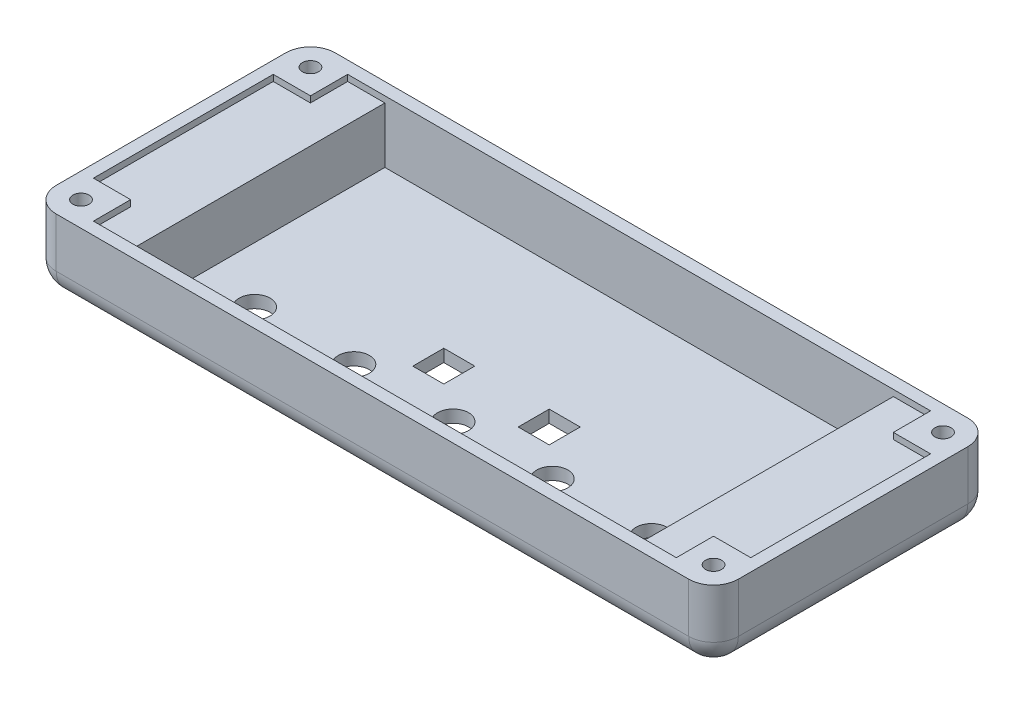
SolidWorks part; units mm, degrees
ref_plane "Front Plane" through (0, 0, 0) normal (0, 0, 1) x (1, 0, 0)
ref_plane "Top Plane" through (0, 0, 0) normal (0, 1, 0) x (1, 0, 0)
ref_plane "Right Plane" through (0, 0, 0) normal (1, 0, 0) x (0, 0, -1)
sketch "Sketch1" plane through (0, 0, 0) normal (0, 1, 0) x (1, 0, 0)
  line L1 (-55, 22.5) -> (55, 22.5)
  line L2 (-55, 22.5) -> (-55, -22.5)
  line L3 (-55, -22.5) -> (55, -22.5)
  line L4 (55, 22.5) -> (55, -22.5)
  line L5 (-55, 22.5) -> (55, -22.5) construction
  line L6 (-55, -22.5) -> (55, 22.5) construction
  point P0 (0, 0)
  dimension "D1" = 45
  dimension "D2" = 110
extrude "Boss-Extrude1" add sketch "Sketch1" along normal blind 2
sketch "Sketch3" plane through (0, 2, 0) normal (0, 1, 0) x (1, 0, 0)
  line L1 (-55, 22.5) -> (55, 22.5)
  line L2 (-55, 22.5) -> (-55, -22.5)
  line L3 (-55, -22.5) -> (55, -22.5)
  line L4 (55, 22.5) -> (55, -22.5)
  line L5 (-55, 22.5) -> (55, -22.5) construction
  line L6 (-55, -22.5) -> (55, 22.5) construction
  line L7 (-53, 20.5) -> (53, 20.5)
  line L8 (-53, 20.5) -> (-53, -20.5)
  line L9 (-53, -20.5) -> (53, -20.5)
  line L10 (53, 20.5) -> (53, -20.5)
  line L11 (-53, 20.5) -> (53, -20.5) construction
  line L12 (-53, -20.5) -> (53, 20.5) construction
  point P0 (0, 0)
  point P7 (0, 0)
  dimension "D1" = 41
  dimension "D2" = 106
extrude "Boss-Extrude2" add sketch "Sketch3" along normal blind 10
sketch "Sketch4" plane through (0, 2, 0) normal (0, 1, 0) x (1, 0, 0)
  line L0 (-53, -20.5) -> (53, -20.5) construction
  line L1 (-53, 20.5) -> (-41, 20.5)
  line L2 (-53, 20.5) -> (-53, -20.5)
  line L3 (-53, -20.5) -> (-41, -20.5)
  line L4 (-41, 20.5) -> (-41, -20.5)
  line L5 (-53, -20.5) -> (53, -20.5) construction
  line L6 (53, 20.5) -> (41, 20.5)
  line L7 (53, 20.5) -> (53, -20.5)
  line L8 (53, -20.5) -> (41, -20.5)
  line L9 (41, 20.5) -> (41, -20.5)
  dimension "D1" = 12
  dimension "D2" = 12
extrude "Boss-Extrude3" add sketch "Sketch4" along normal blind 9
sketch "Sketch5" plane through (0, 11, 0) normal (0, 1, 0) x (1, 0, 0)
  line L1 (-53, 20.5) -> (-47, 20.5)
  line L2 (-53, 20.5) -> (-53, 14.5)
  line L3 (-53, 14.5) -> (-47, 14.5)
  line L4 (-47, 20.5) -> (-47, 14.5)
  line L5 (-53, -20.5) -> (-47, -20.5)
  line L6 (-53, -20.5) -> (-53, -14.5)
  line L7 (-53, -14.5) -> (-47, -14.5)
  line L8 (-47, -20.5) -> (-47, -14.5)
  dimension "D1" = 6
  dimension "D2" = 6
  dimension "D3" = 6
  dimension "D4" = 6
extrude "Boss-Extrude4" add sketch "Sketch5" along normal blind 1
sketch "Sketch6" plane through (0, 11, 0) normal (0, 1, 0) x (1, 0, 0)
  line L1 (53, 20.5) -> (47, 20.5)
  line L2 (53, 20.5) -> (53, 14.5)
  line L3 (53, 14.5) -> (47, 14.5)
  line L4 (47, 20.5) -> (47, 14.5)
  line L5 (53, -20.5) -> (47, -20.5)
  line L6 (53, -20.5) -> (53, -14.5)
  line L7 (53, -14.5) -> (47, -14.5)
  line L8 (47, -20.5) -> (47, -14.5)
  dimension "D1" = 6
  dimension "D2" = 6
  dimension "D3" = 6
  dimension "D4" = 6
extrude "Boss-Extrude5" add sketch "Sketch6" along normal blind 1
fillet "Fillet1" radius 4 4 edges at (55, 6, -22.5) (55, 6, 22.5) (-55, 6, 22.5) (-55, 6, -22.5)
fillet "Fillet2" radius 4 8 edges at (53.8284, 0, 21.3284) (53.8284, 0, -21.3284) (55, 0, 0) (-53.8284, 0, 21.3284) (0, 0, 22.5) (-53.8284, 0, -21.3284) (-55, 0, 0) (0, 0, -22.5)
sketch "Sketch7" plane through (0, 12, 0) normal (0, 1, 0) x (1, 0, 0)
  circle A0 centre (-51, 18.5) radius 1.3
  circle A1 centre (51, 18.5) radius 1.3
  circle A2 centre (51, -18.5) radius 1.3
  circle A3 centre (-51, -18.5) radius 1.3
  dimension "D1" = 2.6
  dimension "D2" = 2.6
  dimension "D3" = 2.6
  dimension "D4" = 2.6
extrude "Cut-Extrude1" cut sketch "Sketch7" against normal blind 8
sketch "Sketch9" plane through (0, 0, 0) normal (0, -1, 0) x (1, 0, 0)
  line L0 (-51, 18.5) -> (-51, -18.5) construction
  line L2 (-51, -18.5) -> (51, -18.5) construction
  line L3 (51, -18.5) -> (51, 18.5) construction
  line L4 (-11, 5) -> (-6, 5)
  line L5 (-11, 5) -> (-11, 0)
  line L6 (-11, 0) -> (-6, 0)
  line L7 (-6, 5) -> (-6, 0)
  line L8 (-11, 5) -> (-6, 0) construction
  line L9 (-11, 0) -> (-6, 5) construction
  line L10 (6, 5) -> (11, 5)
  line L11 (6, 5) -> (6, 0)
  line L12 (6, 0) -> (11, 0)
  line L13 (11, 5) -> (11, 0)
  line L14 (6, 5) -> (11, 0) construction
  line L15 (6, 0) -> (11, 5) construction
  circle A0 centre (-32, 9.5) radius 2.5
  circle A1 centre (-16, 9.5) radius 2.5
  circle A2 centre (0, 9.5) radius 2.5
  circle A3 centre (16, 9.5) radius 2.5
  circle A4 centre (32, 9.5) radius 2.5
  point P16 (-8.5, 2.5)
  point P21 (8.5, 2.5)
  dimension "D1" = 5
  dimension "D2" = 19
  dimension "D3" = 5
  dimension "D4" = 5
  dimension "D5" = 5
  dimension "D6" = 5
  dimension "D9" = 16
  dimension "D10" = 16
  dimension "D12" = 28
  dimension "D13" = 28
  dimension "D14" = 28
  dimension "D15" = 28
  dimension "D16" = 19
  dimension "D11" = 28
  dimension "D21" = 7
  dimension "D24" = 7.5
  dimension "D7" = 16
  dimension "D8" = 16
  dimension "D17" = 5
  dimension "D18" = 5
  dimension "D19" = 5
  dimension "D20" = 5
  dimension "D22" = 0
  dimension "D23" = 12
extrude "Cut-Extrude3" cut sketch "Sketch9" against normal blind 5
sketch "Sketch10" plane through (0, 0, 0) normal (0, -1, 0) x (1, 0, 0)
  line L0 (-51, -18.5) -> (51, -18.5) construction
  line L1 (-51, 18.5) -> (-51, -18.5) construction
  text T0 "STATUS" font "Century Gothic" height 2.5
  text T1 "PREHEAT" font "Century Gothic" height 2.5
  text T2 "SOAK" font "Century Gothic" height 2.5
  text T3 "REFLOW" font "Century Gothic" height 2.5
  text T4 "COOL" font "Century Gothic" height 2.5
  dimension "D1" = 32
  dimension "D2" = 28
  dimension "D3" = 32
  dimension "D4" = 32
  dimension "D5" = 46.5
  dimension "D6" = 61
  dimension "D7" = 32
  dimension "D8" = 32
  dimension "D9" = 79
  dimension "D10" = 13.5
extrude "Cut-Extrude4" cut sketch "Sketch10" against normal blind 1
